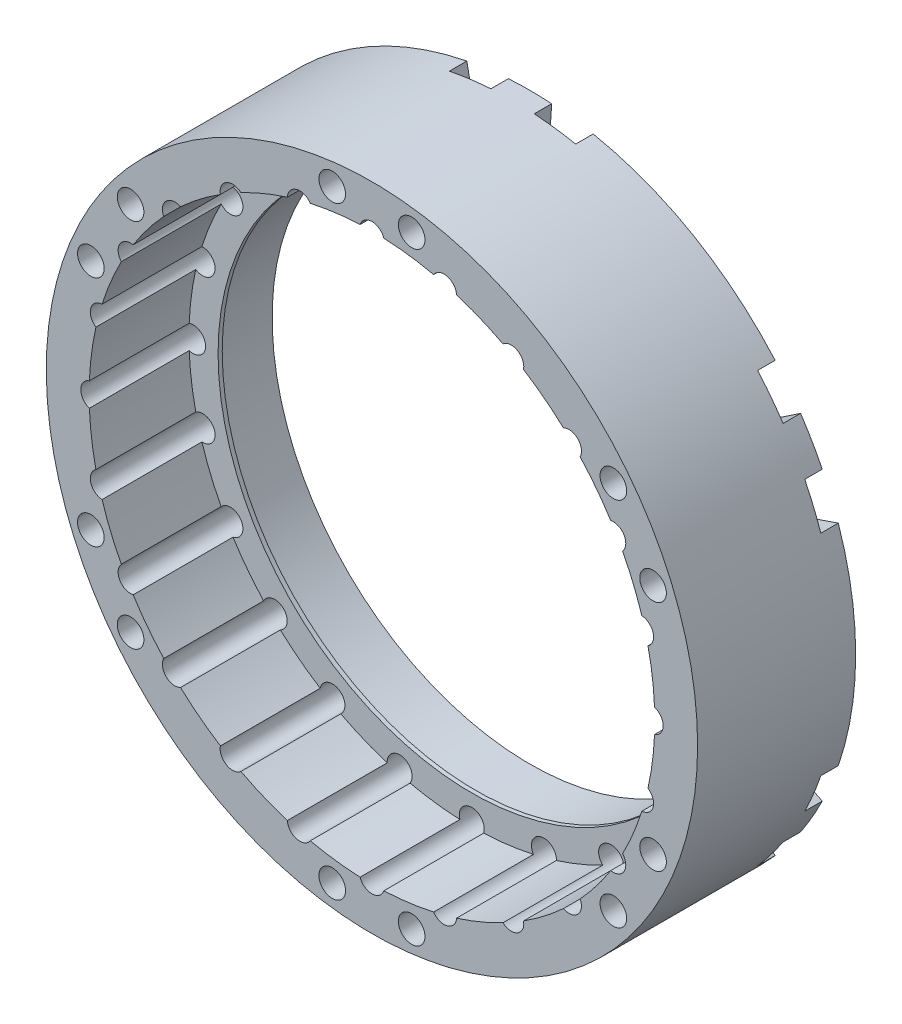
SolidWorks part; units mm, degrees
material "ABS"
ref_plane "Front Plane" through (0, 0, 0) normal (0, 0, 1) x (1, 0, 0)
ref_plane "Top Plane" through (0, 0, 0) normal (0, 1, 0) x (1, 0, 0)
ref_plane "Right Plane" through (0, 0, 0) normal (1, 0, 0) x (0, 0, -1)
sketch "CYC Master Sketch" plane through (0, 0, 0) normal (0, 0, 1) x (1, 0, 0)
  circle A0 centre (0, 0) radius 39.15
  circle A2 centre (0, 0) radius 33.5 construction
  circle A3 centre (-33.5, 0) radius 1.5
  circle A4 centre (-32.3585, 8.6704) radius 1.5
  circle A5 centre (-29.0119, 16.75) radius 1.5
  circle A6 centre (-23.6881, 23.6881) radius 1.5
  circle A7 centre (-16.75, 29.0119) radius 1.5
  circle A8 centre (-8.6704, 32.3585) radius 1.5
  circle A9 centre (0, 33.5) radius 1.5
  circle A10 centre (8.6704, 32.3585) radius 1.5
  circle A11 centre (16.75, 29.0119) radius 1.5
  circle A12 centre (23.6881, 23.6881) radius 1.5
  circle A13 centre (29.0119, 16.75) radius 1.5
  circle A14 centre (32.3585, 8.6704) radius 1.5
  circle A15 centre (33.5, 0) radius 1.5
  circle A16 centre (32.3585, -8.6704) radius 1.5
  circle A17 centre (29.0119, -16.75) radius 1.5
  circle A18 centre (23.6881, -23.6881) radius 1.5
  circle A19 centre (16.75, -29.0119) radius 1.5
  circle A20 centre (8.6704, -32.3585) radius 1.5
  circle A21 centre (0, -33.5) radius 1.5
  circle A22 centre (-8.6704, -32.3585) radius 1.5
  circle A23 centre (0, 0) radius 34
  circle A24 centre (-16.75, -29.0119) radius 1.5
  circle A25 centre (-23.6881, -23.6881) radius 1.5
  circle A26 centre (-29.0119, -16.75) radius 1.5
  circle A27 centre (-32.3585, -8.6704) radius 1.5
  circle A28 centre (0, 0) radius 31 construction
  circle A29 centre (0, 0) radius 25 construction
  circle A30 centre (0, 0) radius 36.575 construction
  circle A31 centre (4.774, -36.2621) radius 1.6
  circle A32 centre (-4.774, -36.2621) radius 1.6
  circle A33 centre (-29.0169, -22.2654) radius 1.6
  circle A34 centre (-33.7909, -13.9966) radius 1.6
  circle A35 centre (-33.7909, 13.9966) radius 1.6
  circle A36 centre (-29.0169, 22.2654) radius 1.6
  circle A37 centre (-4.774, 36.2621) radius 1.6
  circle A38 centre (4.774, 36.2621) radius 1.6
  circle A39 centre (29.0169, 22.2654) radius 1.6
  circle A40 centre (33.7909, 13.9966) radius 1.6
  circle A41 centre (33.7909, -13.9966) radius 1.6
  circle A42 centre (29.0169, -22.2654) radius 1.6
  point P47 (0, 0)
  point P72 (0, 0)
extrude "Gearbox Wall" add sketch "CYC Master Sketch" along normal blind 19 contours A0 A23 A13 A14 A15 A16 A17 A18 A19 A20 A21 A22 A3 A4 A5 A6 A7 A8 A9 A10 A11 A12 region at (-38.0427, 0, 0)
extrude "Gearbox Bottom" add sketch "CYC Master Sketch<3>" along normal blind 7 contours A21 A23 | A23 A20 | A20 A23 | A23 A19 | A19 A23 | A23 A18 | A18 A23 | A23 A17 | A17 A23 | A23 A16 | A16 A23 | A23 A15 | A15 A23 | A23 A14 | A14 A23 | A23 A13 | A13 A23 | A23 A12 | A12 A23 | A23 A11 | A11 A23 | A23 A10 | A10 A23 | A23 A9 | A9 A23 | A23 A8 | A8 A23 | A23 A7 | A7 A23 | A23 A6 | A6 A23 | A23 A5 | A5 A23 | A23 A4 | A4 A23 | A23 A3 | A3 A23 | A23 A22 | A22 A23 | A13 A23 A12 A11 A10 A9 A8 A7 A6 A5 A4 A3 A22 A21 A20 A19 A18 A17 A16 A15 A14 | A24 | A25 | A26 | A27 | A21 region at (-33.1184, 0, 0) region at (0, 0, 0) region at (-34.4085, 0, 0) region at (-31.99, 8.5717, 0) region at (-33.2361, 8.9056, 0) region at (-28.6814, 16.5592, 0) region at (-29.7987, 17.2043, 0) region at (-23.4183, 23.4183, 0) region at (-24.3305, 24.3305, 0) region at (-16.5592, 28.6814, 0) region at (-17.2043, 29.7987, 0) region at (-8.5717, 31.99, 0) region at (-8.9056, 33.2361, 0) region at (-8.9056, -33.2361, 0) region at (-8.5717, -31.99, 0) region at (0, 33.1184, 0) region at (0, 34.4085, 0) region at (0, -33.1184, 0) region at (8.5717, 31.99, 0) region at (8.9056, 33.2361, 0) region at (8.9056, -33.2361, 0) region at (8.5717, -31.99, 0) region at (16.5592, 28.6814, 0) region at (17.2043, 29.7987, 0) region at (17.2043, -29.7987, 0) region at (16.5592, -28.6814, 0) region at (23.4183, 23.4183, 0) region at (24.3305, 24.3305, 0) region at (24.3305, -24.3305, 0) region at (23.4183, -23.4183, 0) region at (28.6814, 16.5592, 0) region at (29.7987, 17.2043, 0) region at (29.7987, -17.2043, 0) region at (28.6814, -16.5592, 0) region at (31.99, 8.5717, 0) region at (33.2361, 8.9056, 0) region at (33.2361, -8.9056, 0) region at (31.99, -8.5717, 0) region at (33.1184, 0, 0) region at (34.4085, 0, 0)
sketch "CYC Master Sketch<3>" plane through (0, 0, 0) normal (0, 0, 1) x (1, 0, 0) same geometry as "CYC Master Sketch"
extrude "Pin Cut" cut sketch "CYC Master Sketch<2>" against normal blind 4 from surface contours A23 A7 | A7 A23 | A23 A6 | A6 A23 | A23 A5 | A5 A23 | A23 A4 | A4 A23 | A23 A3 | A3 A23 | A23 A22 | A22 A23 | A23 A21 | A21 A23 | A23 A20 | A20 A23 | A23 A19 | A19 A23 | A23 A18 | A18 A23 | A23 A17 | A17 A23 | A16 A23 | A23 A16 | A15 A23 | A23 A15 | A23 A14 | A14 A23 | A23 A13 | A13 A23 | A23 A12 | A12 A23 | A23 A11 | A11 A23 | A10 A23 | A23 A9 | A9 A23 | A23 A8 | A8 A23 | A23 A10 | A23 A24 | A23 A24 | A23 A25 | A23 A25 | A23 A26 | A23 A26 | A23 A27 | A23 A27 region at (-33.1184, 0, 0) region at (-34.4085, 0, 0) region at (-31.99, 8.5717, 0) region at (-33.2361, 8.9056, 0) region at (-31.99, -8.5717, 0) region at (-33.2361, -8.9056, 0) region at (-28.6814, 16.5592, 0) region at (-29.7987, 17.2043, 0) region at (-28.6814, -16.5592, 0) region at (-29.7987, -17.2043, 0) region at (-23.4183, 23.4183, 0) region at (-24.3305, 24.3305, 0) region at (-23.4183, -23.4183, 0) region at (-24.3305, -24.3305, 0) region at (-16.5592, 28.6814, 0) region at (-17.2043, 29.7987, 0) region at (-16.5592, -28.6814, 0) region at (-17.2043, -29.7987, 0) region at (-8.5717, 31.99, 0) region at (-8.9056, 33.2361, 0) region at (-8.9056, -33.2361, 0) region at (-8.5717, -31.99, 0) region at (0, 33.1184, 0) region at (0, 34.4085, 0) region at (0, -34.4085, 0) region at (0, -33.1184, 0) region at (8.5717, 31.99, 0) region at (8.9056, 33.2361, 0) region at (8.9056, -33.2361, 0) region at (8.5717, -31.99, 0) region at (16.5592, 28.6814, 0) region at (17.2043, 29.7987, 0) region at (17.2043, -29.7987, 0) region at (16.5592, -28.6814, 0) region at (23.4183, 23.4183, 0) region at (24.3305, 24.3305, 0) region at (24.3305, -24.3305, 0) region at (23.4183, -23.4183, 0) region at (28.6814, 16.5592, 0) region at (29.7987, 17.2043, 0) region at (29.7987, -17.2043, 0) region at (28.6814, -16.5592, 0) region at (31.99, 8.5717, 0) region at (33.2361, 8.9056, 0) region at (33.2361, -8.9056, 0) region at (31.99, -8.5717, 0) region at (33.1184, 0, 0) region at (34.4085, 0, 0) starting at face at (0, 0, 7)
sketch "CYC Master Sketch<2>" plane through (0, 0, 0) normal (0, 0, 1) x (1, 0, 0) same geometry as "CYC Master Sketch"
sketch "CYC Master" plane through (0, 0, 7) normal (0, 0, 1) x (1, 0, 0)
  circle A0 centre (0, 0) radius 39.15
  circle A2 centre (0, 0) radius 33.5 construction
  circle A3 centre (-33.5, 0) radius 1.5
  circle A4 centre (-32.3585, 8.6704) radius 1.5
  circle A5 centre (-29.0119, 16.75) radius 1.5
  circle A6 centre (-23.6881, 23.6881) radius 1.5
  circle A7 centre (-16.75, 29.0119) radius 1.5
  circle A8 centre (-8.6704, 32.3585) radius 1.5
  circle A9 centre (0, 33.5) radius 1.5
  circle A10 centre (8.6704, 32.3585) radius 1.5
  circle A11 centre (16.75, 29.0119) radius 1.5
  circle A12 centre (23.6881, 23.6881) radius 1.5
  circle A13 centre (29.0119, 16.75) radius 1.5
  circle A14 centre (32.3585, 8.6704) radius 1.5
  circle A15 centre (33.5, 0) radius 1.5
  circle A16 centre (32.3585, -8.6704) radius 1.5
  circle A17 centre (29.0119, -16.75) radius 1.5
  circle A18 centre (23.6881, -23.6881) radius 1.5
  circle A19 centre (16.75, -29.0119) radius 1.5
  circle A20 centre (8.6704, -32.3585) radius 1.5
  circle A21 centre (0, -33.5) radius 1.5
  circle A22 centre (-8.6704, -32.3585) radius 1.5
  circle A23 centre (0, 0) radius 34
  circle A24 centre (-16.75, -29.0119) radius 1.5
  circle A25 centre (-23.6881, -23.6881) radius 1.5
  circle A26 centre (-29.0119, -16.75) radius 1.5
  circle A27 centre (-32.3585, -8.6704) radius 1.5
  circle A28 centre (0, 0) radius 31 construction
  circle A29 centre (0, 0) radius 25 construction
  circle A30 centre (0, 0) radius 36.575 construction
  circle A31 centre (4.774, -36.2621) radius 1.6
  circle A32 centre (-4.774, -36.2621) radius 1.6
  circle A33 centre (-29.0169, -22.2654) radius 1.6
  circle A34 centre (-33.7909, -13.9966) radius 1.6
  circle A35 centre (-33.7909, 13.9966) radius 1.6
  circle A36 centre (-29.0169, 22.2654) radius 1.6
  circle A37 centre (-4.774, 36.2621) radius 1.6
  circle A38 centre (4.774, 36.2621) radius 1.6
  circle A39 centre (29.0169, 22.2654) radius 1.6
  circle A40 centre (33.7909, 13.9966) radius 1.6
  circle A41 centre (33.7909, -13.9966) radius 1.6
  circle A42 centre (29.0169, -22.2654) radius 1.6
  point P47 (0, 0)
  point P72 (0, 0)
sketch "Sketch2" plane through (0, 0, 7) normal (0, 0, 1) x (1, 0, 0)
  circle A0 centre (0, 0) radius 31
  circle A1 centre (0, 0) radius 31 construction
extrude "Housing Bearing Cut" cut sketch "Sketch2" against normal through all
sketch "Sketch3" plane through (0, 0, 7) normal (0, 0, 1) x (1, 0, 0)
  circle A0 centre (0, 0) radius 31
  circle A1 centre (0, 0) radius 30.5
  circle A2 centre (0, 0) radius 31 construction
  dimension "D1" = 61
  dimension "Housing Bearing Outer (Driven)" = 62
extrude "Housing Bearing Retainer" add sketch "Sketch3" against normal blind 0.5
sketch "Sketch5" plane through (0, 0, 0) normal (0, 0, -1) x (-1, 0, 0)
  line L0 (0, 0) -> (32.7539, 16.1055) construction
  line L1 (0, 0) -> (34.5488, 11.7722) construction
  line L2 (34.5488, 11.7722) -> (37.0578, 12.6271)
  line L3 (32.7539, 16.1055) -> (35.1325, 17.2751)
  line L4 (0, 0) -> (33.9049, 19.575) construction
  line L5 (27.4695, 24.0341) -> (29.4643, 25.7794)
  line L6 (30.3247, 20.313) -> (32.5269, 21.7881)
  line L7 (34.5488, -11.7722) -> (37.0578, -12.6271)
  line L8 (32.7539, -16.1055) -> (35.1325, -17.2751)
  line L9 (27.4695, -24.0341) -> (29.4643, -25.7794)
  line L10 (30.3247, -20.313) -> (32.5269, -21.7881)
  line L11 (7.0794, -35.8063) -> (7.5935, -38.4065)
  line L12 (2.4292, -36.4185) -> (2.6056, -39.0632)
  line L13 (-7.0794, -35.8063) -> (-7.5935, -38.4065)
  line L14 (-2.4292, -36.4185) -> (-2.6056, -39.0632)
  line L15 (-27.4695, -24.0341) -> (-29.4643, -25.7794)
  line L16 (-30.3247, -20.313) -> (-32.5269, -21.7881)
  line L17 (-34.5488, -11.7722) -> (-37.0578, -12.6271)
  line L18 (-32.7539, -16.1055) -> (-35.1325, -17.2751)
  line L19 (-34.5488, 11.7722) -> (-37.0578, 12.6271)
  line L20 (-32.7539, 16.1055) -> (-35.1325, 17.2751)
  line L21 (-27.4695, 24.0341) -> (-29.4643, 25.7794)
  line L22 (-30.3247, 20.313) -> (-32.5269, 21.7881)
  line L23 (-7.0794, 35.8063) -> (-7.5935, 38.4065)
  line L24 (-2.4292, 36.4185) -> (-2.6056, 39.0632)
  line L25 (7.0794, 35.8063) -> (7.5935, 38.4065)
  line L26 (2.4292, 36.4185) -> (2.6056, 39.0632)
  arc A0 (32.7539, 16.1055) -> (34.5488, 11.7722) centre (33.7909, 13.9966) ccw
  arc A1 (-32.5269, -21.7881) -> (-29.4643, -25.7794) centre (0, 0) ccw
  circle A2 centre (0, 0) radius 39.15 construction
  arc A3 (35.1325, 17.2751) -> (37.0578, 12.6271) centre (0, 0) cw
  arc A4 (32.5269, 21.7881) -> (29.4643, 25.7794) centre (0, 0) ccw
  arc A5 (30.3247, 20.313) -> (27.4695, 24.0341) centre (29.0169, 22.2654) cw
  arc A6 (35.1325, -17.2751) -> (37.0578, -12.6271) centre (0, 0) ccw
  arc A7 (32.7539, -16.1055) -> (34.5488, -11.7722) centre (33.7909, -13.9966) cw
  arc A8 (32.5269, -21.7881) -> (29.4643, -25.7794) centre (0, 0) cw
  arc A9 (30.3247, -20.313) -> (27.4695, -24.0341) centre (29.0169, -22.2654) ccw
  arc A10 (2.6056, -39.0632) -> (7.5935, -38.4065) centre (0, 0) ccw
  arc A11 (2.4292, -36.4185) -> (7.0794, -35.8063) centre (4.774, -36.2621) cw
  arc A12 (-2.6056, -39.0632) -> (-7.5935, -38.4065) centre (0, 0) cw
  arc A13 (-2.4292, -36.4185) -> (-7.0794, -35.8063) centre (-4.774, -36.2621) ccw
  arc A14 (-30.3247, -20.313) -> (-27.4695, -24.0341) centre (-29.0169, -22.2654) cw
  arc A15 (-35.1325, -17.2751) -> (-37.0578, -12.6271) centre (0, 0) cw
  arc A16 (-32.7539, -16.1055) -> (-34.5488, -11.7722) centre (-33.7909, -13.9966) ccw
  arc A17 (-35.1325, 17.2751) -> (-37.0578, 12.6271) centre (0, 0) ccw
  arc A18 (-32.7539, 16.1055) -> (-34.5488, 11.7722) centre (-33.7909, 13.9966) cw
  arc A19 (-32.5269, 21.7881) -> (-29.4643, 25.7794) centre (0, 0) cw
  arc A20 (-30.3247, 20.313) -> (-27.4695, 24.0341) centre (-29.0169, 22.2654) ccw
  arc A21 (-2.6056, 39.0632) -> (-7.5935, 38.4065) centre (0, 0) ccw
  arc A22 (-2.4292, 36.4185) -> (-7.0794, 35.8063) centre (-4.774, 36.2621) cw
  arc A23 (2.6056, 39.0632) -> (7.5935, 38.4065) centre (0, 0) cw
  arc A24 (2.4292, 36.4185) -> (7.0794, 35.8063) centre (4.774, 36.2621) ccw
  point P39 (0, 0)
  dimension "D1" = 4.7
  dimension "D3" = 6
  dimension "D2" = 7.5
extrude "M3 Socket Head Cutout" cut sketch "Sketch5" against normal blind 2.1
fillet "Fillet1" radius 0.4 12 edges at (-7.5935, -38.4065, 1.05) (-2.6056, -39.0632, 1.05) (2.6056, -39.0632, 1.05) (7.5935, -38.4065, 1.05) (-29.4643, -25.7794, 1.05) (-32.5269, -21.7881, 1.05) (-37.0578, -12.6271, 1.05) (-35.1325, -17.2751, 1.05) (-29.4643, 25.7794, 1.05) (-32.5269, 21.7881, 1.05) (-35.1325, 17.2751, 1.05) (-37.0578, 12.6271, 1.05)
equation "\"D1@Sketch3\" = \"Housing Bearing Outer (Driven)@Sketch3\" - 1"
